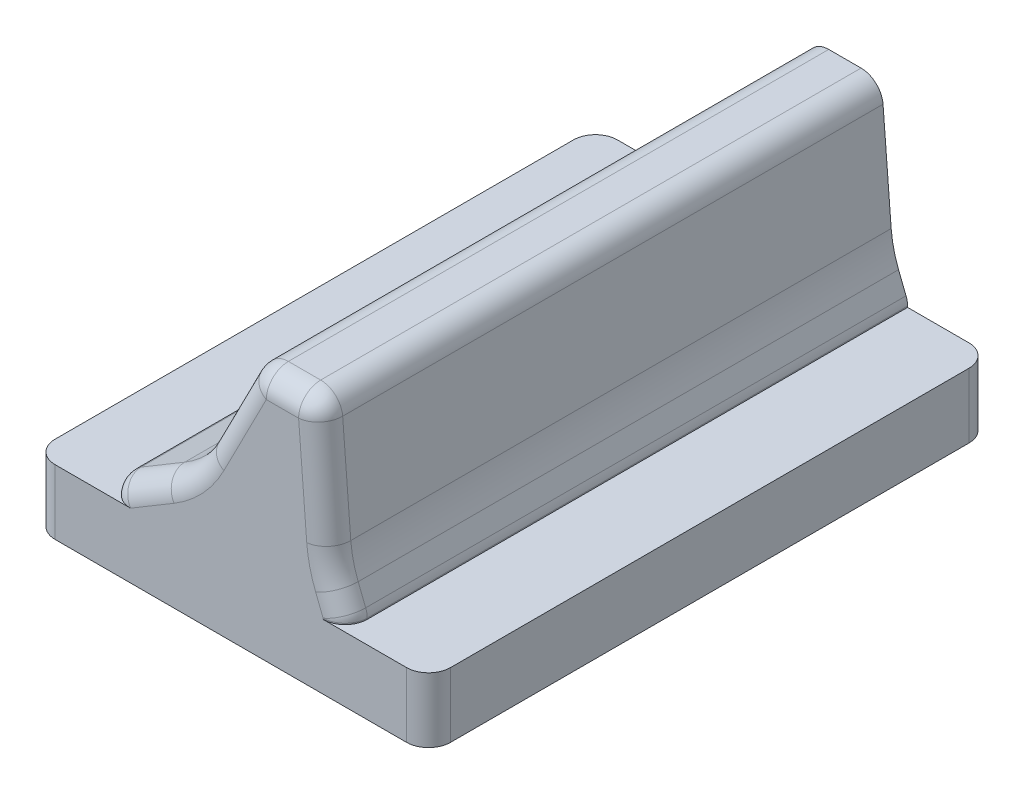
SolidWorks part; units mm, degrees
ref_plane "Plan de face" through (0, 0, 0) normal (0, 0, 1) x (1, 0, 0)
ref_plane "Plan de dessus" through (0, 0, 0) normal (0, 1, 0) x (1, 0, 0)
ref_plane "Plan de droite" through (0, 0, 0) normal (1, 0, 0) x (0, 0, -1)
sketch "Esquisse2" plane through (0, 0, 0) normal (0, 0, 1) x (1, 0, 0)
  line L0 (-4, 0) -> (-4, -1) construction
  line L1 (-8, 1) -> (-8, 0) construction
  line L2 (-8, 1) -> (-1, 1) construction
  line L3 (-8, 0) -> (-1, 0) construction
  line L4 (4, -1) -> (4, 0) construction
  line L5 (1, 0) -> (8, 0) construction
  line L6 (8, 1) -> (8, 0) construction
  line L7 (1, 1) -> (8, 1) construction
  line L8 (4, 1) -> (4, 1.5) construction
  line L9 (2.798, 9) -> (1.798, 9) construction
  line L10 (-4, 1.202) -> (-4, 1) construction
  line L11 (-4, 0) -> (-4, -1)
  line L12 (-8, 1) -> (-8, 0)
  line L13 (-8, 1) -> (-4, 1)
  line L14 (-8, 0) -> (-4, 0)
  line L15 (4, -1) -> (4, 0)
  line L16 (4, 0) -> (8, 0)
  line L17 (8, 1) -> (8, 0)
  line L18 (4, 1) -> (8, 1)
  line L19 (4, 1) -> (4, 1.5)
  line L20 (2.798, 9) -> (1.798, 9)
  line L21 (-4, 1.202) -> (-4, 1)
  line L22 (-4, -1) -> (-4, -1.4124)
  line L23 (-5.0604, 2.3837) -> (-3.0886, 3.5606)
  line L24 (-1.2015, 5.5732) -> (0.7212, 9.324)
  line L25 (1.6111, 9.8678) -> (3.0754, 9.8678)
  line L26 (4.0724, 8.9461) -> (4.4412, 4.2487)
  line L27 (4.7761, 2.8016) -> (5.1153, 1.9437)
  line L28 (5.1854, 1.576) -> (5.1854, 1.525)
  line L29 (-5.5479, 1.525) -> (-8.9662, 1.525)
  line L30 (5.5479, 1.525) -> (8.9662, 1.525)
  line L31 (0, 0) -> (0, 9.324) construction
  line L32 (-8.9662, 1.525) -> (-8.9662, -1.4124)
  line L33 (8.9662, 1.525) -> (8.9662, -1.4124)
  line L34 (-8.9662, -1.4124) -> (-4, -1.4124)
  line L35 (8.9662, -1.4124) -> (4, -1.4124)
  line L41 (5.5479, 1.525) -> (5.1854, 1.525)
  line L42 (4, -1) -> (4, -1.4124)
  arc A0 (4, 1.5) -> (3.6, 2.3) centre (3, 1.5) ccw construction
  arc A1 (3.035, 3.8221) -> (3.6, 2.3) centre (4.5, 3.5) ccw construction
  arc A2 (3.035, 3.8221) -> (2.798, 9) centre (-6.7317, 5.9694) ccw construction
  arc A3 (-3.4545, 2.0928) -> (1.798, 9) centre (-8, 11) ccw construction
  arc A4 (-3.4545, 2.0928) -> (-4, 1.202) centre (-3, 1.202) ccw construction
  arc A5 (4, 1.5) -> (3.6, 2.3) centre (3, 1.5) ccw
  arc A6 (3.035, 3.8221) -> (3.6, 2.3) centre (4.5, 3.5) ccw
  arc A7 (3.035, 3.8221) -> (2.798, 9) centre (-6.7317, 5.9694) ccw
  arc A8 (-3.4545, 2.0928) -> (1.798, 9) centre (-8, 11) ccw
  arc A9 (-3.4545, 2.0928) -> (-4, 1.202) centre (-3, 1.202) ccw
  arc A10 (-3.0886, 3.5606) -> (-1.2015, 5.5732) centre (-5.651, 7.854) ccw
  arc A11 (4.7761, 2.8016) -> (4.4412, 4.2487) centre (9.4259, 4.6401) cw
  arc A12 (-5.5479, 1.525) -> (-5.0604, 2.3837) centre (-4.5479, 1.525) cw
  arc A13 (5.1153, 1.9437) -> (5.1854, 1.576) centre (4.1854, 1.576) cw
  arc A14 (0.7212, 9.324) -> (1.6111, 9.8678) centre (1.6111, 8.8678) cw
  arc A15 (4.0724, 8.9461) -> (3.0754, 9.8678) centre (3.0754, 8.8678) ccw
  dimension "D1" = 5
  dimension "D2" = 5
  dimension "D3" = 1
extrude "Extrusion1" add sketch "Esquisse2" against normal blind 24
sketch "Esquisse3" plane through (0, 0, 0) normal (0, 0, 1) x (1, 0, 0)
  line L0 (-4, -1.4124) -> (4, -1.4124)
  line L23 (-4, 0) -> (-8, 0)
  line L24 (-8, 0) -> (-8, 1)
  line L25 (-8, 1) -> (-4, 1)
  line L26 (-4, 1) -> (-4, 1.202)
  line L27 (1.798, 9) -> (2.798, 9)
  line L28 (4, 1.5) -> (4, 1)
  line L29 (4, 1) -> (8, 1)
  line L30 (8, 1) -> (8, 0)
  line L31 (8, 0) -> (4, 0)
  line L32 (4, 0) -> (4, -1.4124)
  line L33 (4, -1.4124) -> (8.9662, -1.4124)
  line L34 (8.9662, -1.4124) -> (8.9662, 1.525)
  line L35 (8.9662, 1.525) -> (5.1854, 1.525)
  line L36 (5.1854, 1.525) -> (5.1854, 1.576)
  line L37 (5.1153, 1.9437) -> (4.7761, 2.8016)
  line L38 (4.4412, 4.2487) -> (4.0724, 8.9461)
  line L39 (3.0754, 9.8678) -> (1.6111, 9.8678)
  line L40 (0.7212, 9.324) -> (-1.2015, 5.5732)
  line L41 (-3.0886, 3.5606) -> (-5.0604, 2.3837)
  line L42 (-5.5479, 1.525) -> (-8.9662, 1.525)
  line L43 (-8.9662, 1.525) -> (-8.9662, -1.4124)
  line L44 (-8.9662, -1.4124) -> (-4, -1.4124)
  line L45 (-4, -1.4124) -> (-4, 0)
  line L56 (4, -1.4124) -> (8.9662, -1.4124)
  line L57 (8.9662, -1.4124) -> (8.9662, 1.525)
  line L58 (8.9662, 1.525) -> (5.1854, 1.525)
  line L59 (5.1854, 1.525) -> (5.1854, 1.576)
  line L60 (5.1153, 1.9437) -> (4.7761, 2.8016)
  line L61 (4.4412, 4.2487) -> (4.0724, 8.9461)
  line L62 (3.0754, 9.8678) -> (1.6111, 9.8678)
  line L63 (0.7212, 9.324) -> (-1.2015, 5.5732)
  line L64 (-3.0886, 3.5606) -> (-5.0604, 2.3837)
  line L65 (-5.5479, 1.525) -> (-8.9662, 1.525)
  line L66 (-8.9662, 1.525) -> (-8.9662, -1.4124)
  line L67 (-8.9662, -1.4124) -> (-4, -1.4124)
  arc A11 (-3.4545, 2.0928) -> (-4, 1.202) centre (-3, 1.202) ccw
  arc A12 (-3.4545, 2.0928) -> (1.798, 9) centre (-8, 11) ccw
  arc A13 (3.035, 3.8221) -> (2.798, 9) centre (-6.7317, 5.9694) ccw
  arc A14 (3.035, 3.8221) -> (3.6, 2.3) centre (4.5, 3.5) ccw
  arc A15 (4, 1.5) -> (3.6, 2.3) centre (3, 1.5) ccw
  arc A16 (5.1854, 1.576) -> (5.1153, 1.9437) centre (4.1854, 1.576) ccw
  arc A17 (4.4412, 4.2487) -> (4.7761, 2.8016) centre (9.4259, 4.6401) ccw
  arc A18 (4.0724, 8.9461) -> (3.0754, 9.8678) centre (3.0754, 8.8678) ccw
  arc A19 (1.6111, 9.8678) -> (0.7212, 9.324) centre (1.6111, 8.8678) ccw
  arc A20 (-3.0886, 3.5606) -> (-1.2015, 5.5732) centre (-5.651, 7.854) ccw
  arc A21 (-5.0604, 2.3837) -> (-5.5479, 1.525) centre (-4.5479, 1.525) ccw
  arc A27 (5.1854, 1.576) -> (5.1153, 1.9437) centre (4.1854, 1.576) ccw
  arc A28 (4.4412, 4.2487) -> (4.7761, 2.8016) centre (9.4259, 4.6401) ccw
  arc A29 (4.0724, 8.9461) -> (3.0754, 9.8678) centre (3.0754, 8.8678) ccw
  arc A30 (1.6111, 9.8678) -> (0.7212, 9.324) centre (1.6111, 8.8678) ccw
  arc A31 (-3.0886, 3.5606) -> (-1.2015, 5.5732) centre (-5.651, 7.854) ccw
  arc A32 (-5.0604, 2.3837) -> (-5.5479, 1.525) centre (-4.5479, 1.525) ccw
  dimension "D1" = 0
extrude "Extrusion2" add sketch "Esquisse3" along normal blind 1.5
fillet "Congé2" radius 1 16 edges at (5.1854, 1.5505, 1.5) (5.1677, 1.7632, 1.5) (4.9457, 2.3727, 1.5) (4.5546, 3.5126, 1.5) (4.2568, 6.5974, 1.5) (3.7543, 9.6021, 1.5) (-5.4176, 2.0187, 1.5) (-4.0745, 2.9721, 1.5) (-2.0035, 4.4341, 1.5) (-0.2402, 7.4486, 1.5) (1.0897, 9.7211, 1.5) (2.3433, 9.8678, 1.5) (-8.9662, 0.0563, 1.5) (8.9662, 0.0563, 1.5) (-8.9662, 0.0563, -24) (8.9662, 0.0563, -24)
